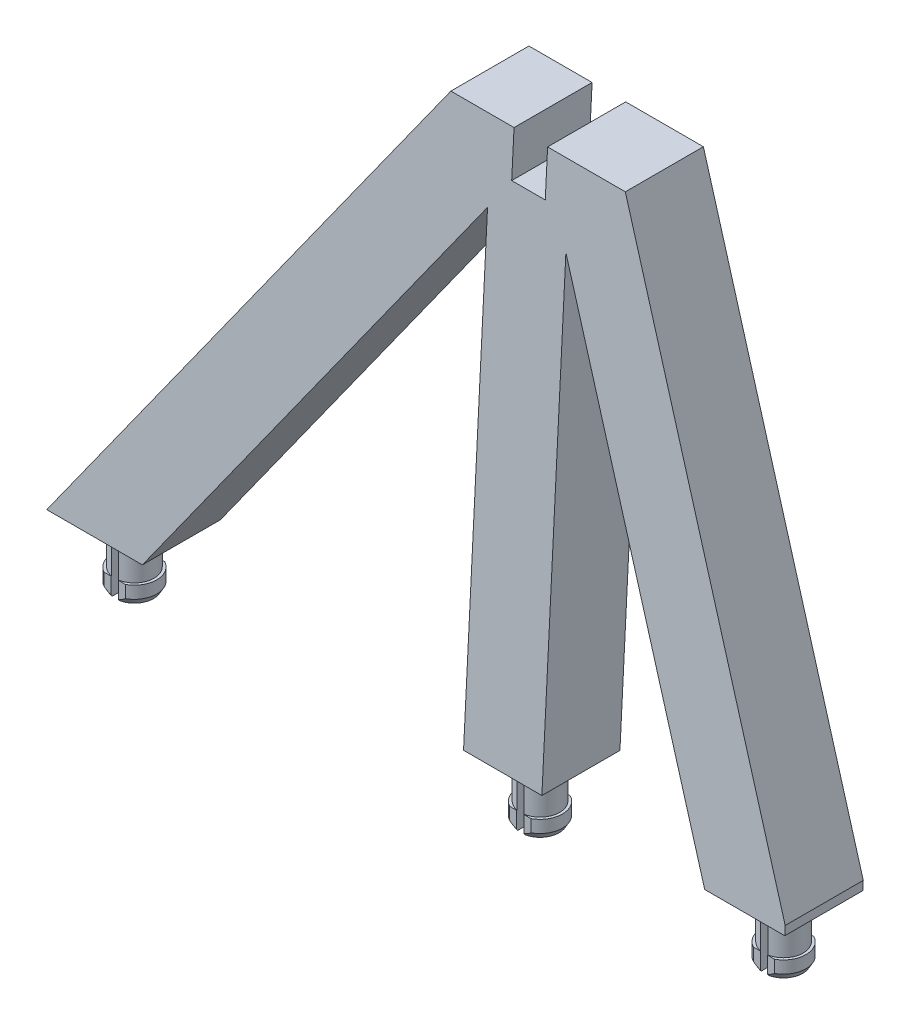
SolidWorks part; units mm, degrees
ref_plane "Front Plane" through (0, 0, 0) normal (0, 0, 1) x (1, 0, 0)
ref_plane "Top Plane" through (0, 0, 0) normal (0, 1, 0) x (1, 0, 0)
ref_plane "Right Plane" through (0, 0, 0) normal (1, 0, 0) x (0, 0, -1)
sketch "Sketch1" plane through (0, 0, 0) normal (0, 1, 0) x (1, 0, 0)
  line L1 (-29.4845, 5.7636) -> (-4.0845, 5.7636) construction
  dimension "D1" = 25.4
ref_plane "Plane1" through (0, -0.3012, -5.7478) normal (0, 0.0523, 0.9986) x (1, 0, 0)
sketch "Sketch2" plane through (0, -0.3012, -5.7478) normal (0, 0.0523, 0.9986) x (1, 0, 0)
  line L0 (-31.9919, 0.3016) -> (-59.0325, 76.5016)
  line L1 (-29.4845, 0.3016) -> (-4.0845, 0.3016) construction
  line L2 (-59.0325, 76.5016) -> (-83.7789, 76.5016)
  line L3 (-83.7789, 76.5016) -> (-137.1172, 0.3016)
  line L4 (-137.1172, 0.3016) -> (-123.5528, 0.3016)
  line L5 (-123.5528, 0.3016) -> (-77.993, 65.3891)
  line L7 (-66.8805, 65.3891) -> (-43.7834, 0.3016)
  line L8 (-43.7834, 0.3016) -> (-31.9919, 0.3016)
  line L9 (-55.9848, 34.6853) -> (-45.5122, 38.4016) construction
  line L10 (-77.993, 65.3891) -> (-77.993, 76.5016) construction
  line L11 (-101.3442, 32.0292) -> (-110.448, 38.4016) construction
  line L12 (-66.8805, 65.3891) -> (-66.8805, 0.3016)
  line L13 (-66.8805, 0.3016) -> (-77.993, 0.3016)
  line L14 (-77.993, 0.3016) -> (-77.993, 65.3891)
  line L15 (-77.993, 32.8454) -> (-66.8805, 32.8454) construction
  point P8 (-130.335, 0.3016)
  point P12 (-72.4367, 0.3016)
  point P17 (-37.8877, 0.3016)
  dimension "D1" = 34.5491
  dimension "D2" = 57.8983
  dimension "D3" = 76.2
  dimension "D4" = 11.1125
ref_plane "Plane3" through (0, 0, 0) normal (0, 0, 1) x (1, 0, 0)
extrude "Boss-Extrude2" add sketch "Sketch2" along direction (0, 0, 1) on the side of the normal blind 11.0744
sketch "Sketch3" plane through (0, 0, 0) normal (0, 0, 1) x (1, 0, 0)
  line L0 (-74.818, 76.0956) -> (-74.818, 69.7456)
  line L1 (-59.0325, 76.0956) -> (-83.7789, 76.0956) construction
  line L2 (-74.818, 69.7456) -> (-70.0555, 69.7456)
  line L3 (-70.0555, 69.7456) -> (-70.0555, 76.0956)
  line L4 (-70.0555, 76.0956) -> (-74.818, 76.0956)
  line L5 (-72.4367, 76.0956) -> (-72.4367, 69.7456) construction
  line L6 (-74.818, 72.9206) -> (-70.0555, 72.9206) construction
  line L7 (-77.993, 76.0956) -> (-66.8805, 76.0956) construction
  line L8 (-77.993, 64.9983) -> (-77.993, 0) construction
  line L9 (-66.8805, 0) -> (-66.8805, 64.9983) construction
  dimension "D1" = 4.7625
  dimension "D2" = 6.35
extrude "Cut-Extrude1" cut sketch "Sketch3" against normal through all both and the other way through all
sketch "Sketch12" plane through (0, 0, 0) normal (0, 0, 1) x (1, 0, 0)
  line L0 (-137.1172, 0) -> (-123.5528, 0) construction
  line L2 (-32.4296, 1.27) -> (-31.1596, 1.27)
  line L3 (-32.4296, 1.27) -> (-32.4296, 0)
  line L4 (-32.4296, 0) -> (-31.1596, 0)
  line L5 (-150.6902, 12.7) -> (-137.9902, 12.7)
  line L6 (-150.6902, 12.7) -> (-150.6902, 0)
  line L7 (-150.6902, 0) -> (-137.9902, 0)
  line L8 (-137.9902, 12.7) -> (-137.9902, 0)
  line L9 (-31.1596, 1.27) -> (-31.1596, 0)
  line L10 (-29.4845, 0) -> (-4.0845, 0) construction
  dimension "D1" = 12.7
  dimension "D2" = 12.7
  dimension "D3" = 14.4374
  dimension "D4" = 1.27
  dimension "D5" = 1.27
  dimension "D6" = 11.3538
extrude "Cut-Extrude6" cut sketch "Sketch12" against normal through all both and the other way through all
shell "Shell13" thickness 2.54 removed face at (-72.7745, 38.3401, -7.7729)
sketch "Sketch13" plane through (0, 0, 0) normal (0, -1, 0) x (1, 0, 0)
  line L0 (-137.1172, 5.3108) -> (-137.1172, -5.7636) construction
  line L3 (-32.4296, -0.2264) -> (-43.7834, -0.2264) construction
  line L4 (-32.4296, -5.7636) -> (-32.4296, 5.3108) construction
  line L5 (-43.7834, 5.3108) -> (-43.7834, -5.7636) construction
  line L6 (-66.8805, -0.2264) -> (-78.4814, -0.2264) construction
  line L7 (-66.8805, 5.3108) -> (-66.8805, -5.7636) construction
  line L11 (-137.1172, -0.2264) -> (-123.5528, -0.2264) construction
  line L13 (-123.5528, 5.3108) -> (-123.5528, -5.7636) construction
  circle A0 centre (-130.216, -0.2264) radius 2.794
  circle A1 centre (-72.681, -0.2264) radius 2.794
  circle A2 centre (-38.1319, -0.2264) radius 2.794
  dimension "D1" = 5.588
  dimension "D2" = 34.5491
  dimension "D3" = 5.7023
  dimension "D4" = 6.9012
extrude "Boss-Extrude3" add sketch "Sketch13" along normal blind 6.35
sketch "Sketch14" plane through (0, -6.35, 0) normal (0, -1, 0) x (1, 0, 0)
  circle A0 centre (-130.216, -0.2264) radius 3.175
  circle A1 centre (-72.681, -0.2264) radius 3.175
  circle A2 centre (-38.1319, -0.2264) radius 3.175
  dimension "D1" = 6.35
extrude "Boss-Extrude4" add sketch "Sketch14" along normal blind 2.54
sketch "Sketch15" plane through (0, -8.89, 0) normal (0, -1, 0) x (1, 0, 0)
  line L0 (-130.216, 2.9486) -> (-130.216, -3.4014) construction
  line L1 (-130.724, 2.9486) -> (-129.708, 2.9486)
  line L2 (-130.724, 2.9486) -> (-130.724, -3.4014)
  line L3 (-130.724, -3.4014) -> (-129.708, -3.4014)
  line L4 (-129.708, 2.9486) -> (-129.708, -3.4014)
  line L5 (-72.681, 2.9486) -> (-72.681, -3.4014)
  line L6 (-73.189, 2.9486) -> (-72.173, 2.9486)
  line L7 (-73.189, 2.9486) -> (-73.189, -3.4014)
  line L8 (-73.189, -3.4014) -> (-72.173, -3.4014)
  line L9 (-72.173, 2.9486) -> (-72.173, -3.4014)
  line L10 (-38.1319, 2.9486) -> (-38.1319, -3.4014)
  line L11 (-38.6399, 2.9486) -> (-37.6239, 2.9486)
  line L12 (-38.6399, 2.9486) -> (-38.6399, -3.4014)
  line L13 (-38.6399, -3.4014) -> (-37.6239, -3.4014)
  line L14 (-37.6239, 2.9486) -> (-37.6239, -3.4014)
  line L16 (-131.7241, 2.9486) -> (-128.708, 2.9486)
  line L17 (-131.7241, 2.9486) -> (-131.7241, 2.5676)
  line L18 (-131.7241, 2.5676) -> (-128.708, 2.5676)
  line L19 (-128.708, 2.9486) -> (-128.708, 2.5676)
  line L20 (-131.7241, -3.4014) -> (-128.708, -3.4014)
  line L21 (-131.7241, -3.4014) -> (-131.7241, -3.0204)
  line L22 (-131.7241, -3.0204) -> (-128.708, -3.0204)
  line L23 (-128.708, -3.4014) -> (-128.708, -3.0204)
  line L24 (-74.189, 2.9486) -> (-71.1729, 2.9486)
  line L25 (-74.189, 2.9486) -> (-74.189, 2.5676)
  line L26 (-74.189, 2.5676) -> (-71.1729, 2.5676)
  line L27 (-71.1729, 2.9486) -> (-71.1729, 2.5676)
  line L28 (-74.189, -3.4014) -> (-71.1729, -3.4014)
  line L29 (-74.189, -3.4014) -> (-74.189, -3.0204)
  line L30 (-74.189, -3.0204) -> (-71.1729, -3.0204)
  line L31 (-71.1729, -3.4014) -> (-71.1729, -3.0204)
  line L32 (-39.6399, -3.4014) -> (-36.6238, -3.4014)
  line L33 (-39.6399, -3.4014) -> (-39.6399, -3.0204)
  line L34 (-39.6399, -3.0204) -> (-36.6238, -3.0204)
  line L35 (-36.6238, -3.4014) -> (-36.6238, -3.0204)
  line L36 (-39.6399, 2.9486) -> (-36.6238, 2.9486)
  line L37 (-39.6399, 2.9486) -> (-39.6399, 2.5676)
  line L38 (-39.6399, 2.5676) -> (-36.6238, 2.5676)
  line L39 (-36.6238, 2.9486) -> (-36.6238, 2.5676)
  circle A0 centre (-130.216, -0.2264) radius 3.175 construction
  circle A1 centre (-72.681, -0.2264) radius 3.175 construction
  circle A2 centre (-38.1319, -0.2264) radius 3.175 construction
  circle A3 centre (-130.216, -0.2264) radius 2.794 construction
  circle A4 centre (-72.681, -0.2264) radius 2.794 construction
  circle A5 centre (-38.1319, -0.2264) radius 2.794 construction
  dimension "D1" = 1.016
extrude "Cut-Extrude7" cut sketch "Sketch15" against normal up to surface (8.89 mm away) contours L2 L3 L4 L1 | L12 L13 L14 L11 | L7 L8 L9 L6 | L20 L23 L22 L21 | L16 L19 L18 L17 | L24 L27 L26 L25 | L30 L31 L28 L29 | L36 L39 L38 L37 | L34 L35 L32 L33 up to face at (-133.01, 0, -0.2264)
sketch "Sketch17" plane through (0, 0.1446, 2.7597) normal (0, -0.0523, -0.9986) x (-1, 0, 0)
  line L2 (72.4367, 55.6289) -> (72.4367, 67.153) construction
  line L3 (75.453, 67.153) -> (69.4205, 67.153) construction
  circle A0 centre (72.4367, 55.6289) radius 3.9687
  dimension "D2" = 7.9375
  dimension "D1" = 11.5241
extrude "Boss-Extrude5" add sketch "Sketch17" along direction (0, 0, 1) on the side of the normal blind 16.444
ref_plane "Plane4" through (0, 56.2734, 0) normal (0, 1, 0) x (1, 0, 0)
sketch "Sketch18" plane through (0, 56.2734, 0) normal (0, 1, 0) x (1, 0, 0)
  line L0 (-68.468, 8.6826) -> (-68.468, 16.5956) construction
  circle A0 centre (-69.8015, 12.4046) radius 2.3813
  ellipse E0 centre (-72.4367, 16.5956) end of major axis (-68.468, 16.5956) minor radius 0.2077 construction
  dimension "D1" = 4.7625
  dimension "D2" = 1.3335
  dimension "D3" = 4.191
extrude "Cut-Extrude9" cut sketch "Sketch18" against normal mid plane 10.668
chamfer "Chamfer1" distance 0.7937 angle 30 6 edges at (-133.391, -8.89, -0.2264) (-127.041, -8.89, -0.2264) (-75.856, -8.89, -0.2264) (-69.506, -8.89, -0.2264) (-41.3069, -8.89, -0.2264) (-34.9569, -8.89, -0.2264) first distance on face at (-132.5576, -7.62, -0.2264) first distance on face at (-127.8745, -7.62, -0.2264) first distance on face at (-75.0225, -7.62, -0.2264) first distance on face at (-70.3394, -7.62, -0.2264) first distance on face at (-40.4734, -7.62, -0.2264) first distance on face at (-35.7904, -7.62, -0.2264)
sketch "Sketch19" plane through (0, -0.3012, -5.7478) normal (0, -0.0523, -0.9986) x (-1, 0, 0)
  line L0 (69.4205, 67.5994) -> (75.453, 67.5994)
  line L1 (75.453, 67.5994) -> (75.453, 2.8451)
  line L2 (75.453, 2.8451) -> (69.4205, 2.8451)
  line L3 (69.4205, 2.8451) -> (69.4205, 67.5994)
  line L4 (77.358, 73.9582) -> (77.358, 70.7276)
  line L5 (77.358, 70.7276) -> (124.8743, 2.8451)
  line L6 (124.8743, 2.8451) -> (132.235, 2.8451)
  line L7 (132.235, 2.8451) -> (82.4574, 73.9582)
  line L8 (82.4574, 73.9582) -> (77.358, 73.9582)
  line L9 (67.2257, 73.9582) -> (41.9904, 2.8451)
  line L10 (41.9904, 2.8451) -> (35.5901, 2.8451)
  line L11 (35.5901, 2.8451) -> (60.8255, 73.9582)
  line L12 (60.8255, 73.9582) -> (67.2257, 73.9582)
extrude "Boss-Extrude11" add sketch "Sketch19" along direction (0, 0, -1) on the side against the normal up to surface (8.5192 mm away) up to face at (-51.4079, 38.0478, 0.7733)
